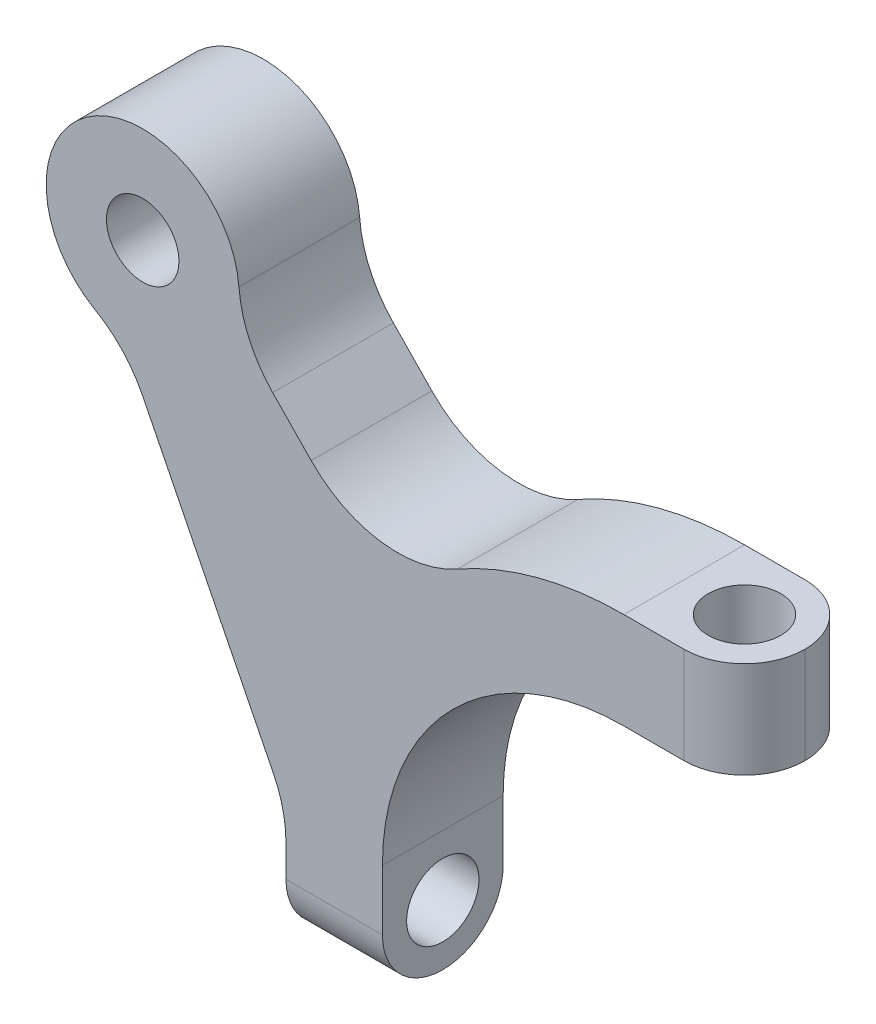
SolidWorks part; units mm, degrees
material "1060 合金"
ref_plane "前视基准面" through (0, 0, 0) normal (0, 0, 1) x (1, 0, 0)
ref_plane "上视基准面" through (0, 0, 0) normal (0, 1, 0) x (1, 0, 0)
ref_plane "右视基准面" through (0, 0, 0) normal (1, 0, 0) x (0, 0, -1)
other "Configuration Table"
sketch "草图1" plane through (0, 0, 0) normal (0, 0, 1) x (1, 0, 0)
  line L1 (0, -55) -> (0, 55) construction
  line L3 (55, 0) -> (-55, 0) construction
  line L4 (0, 9.9987) -> (4.9961, 9.9987)
  line L5 (-10.0019, 0) -> (-10.0019, -4.997)
  line L6 (-10.0019, -4.997) -> (-13.9979, -4.997)
  line L7 (-13.9979, -4.997) -> (-13.9979, 0)
  line L8 (4.9961, 9.9987) -> (4.9961, 13.9979)
  line L9 (4.9961, 13.9979) -> (0, 13.9979)
  arc A0 (-10.0019, 0) -> (0, 9.9987) centre (-0.0032, 0) cw
  arc A1 (0, 13.9979) -> (-13.9979, 0) centre (0, 0) ccw
extrude "凸台-拉伸1" add sketch "草图1" along normal mid plane 5
fillet "圆角1" radius 2.5 4 edges at (-11.9999, -4.997, -2.5) (-11.9999, -4.997, 2.5) (4.9961, 11.9983, -2.5) (4.9961, 11.9983, 2.5)
sketch "草图4" plane through (0, 13.9979, 0) normal (0, 1, 0) x (1, 0, 0)
  circle A0 centre (2.4961, 0) radius 1.5012
extrude "切除-拉伸2" cut sketch "草图4" against normal blind 5
sketch "草图5" plane through (-13.9979, 0, 0) normal (-1, 0, 0) x (0, 0, 1)
  circle A0 centre (0, -2.497) radius 1.4998
extrude "切除-拉伸3" cut sketch "草图5" against normal blind 5
sketch "草图6" plane through (0, 0, -2.5) normal (0, 0, -1) x (-1, 0, 0)
  line L1 (2.75, 0) -> (-2.75, 0) construction
  line L6 (9.8984, 9.8976) -> (16.108, 16.2911)
  line L7 (13.9979, 0) -> (20.7724, 13.5498)
  arc A0 (13.9979, 0) -> (0, 13.9979) centre (0, 0) ccw construction
  arc A1 (13.9979, 0) -> (9.8984, 9.8976) centre (0, 0) ccw
  arc A2 (16.108, 16.2911) -> (20.7724, 13.5498) centre (19.9326, 17.4598) cw
  circle A3 centre (19.9326, 17.4598) radius 1.5008
extrude "凸台-拉伸2" add sketch "草图6" against normal blind 5
fillet "圆角2" radius 5 4 edges at (-20.7724, 13.5498, 0) (-16.108, 16.2911, 0) (-9.8984, 9.8976, 0) (-13.9979, 0, 0)
